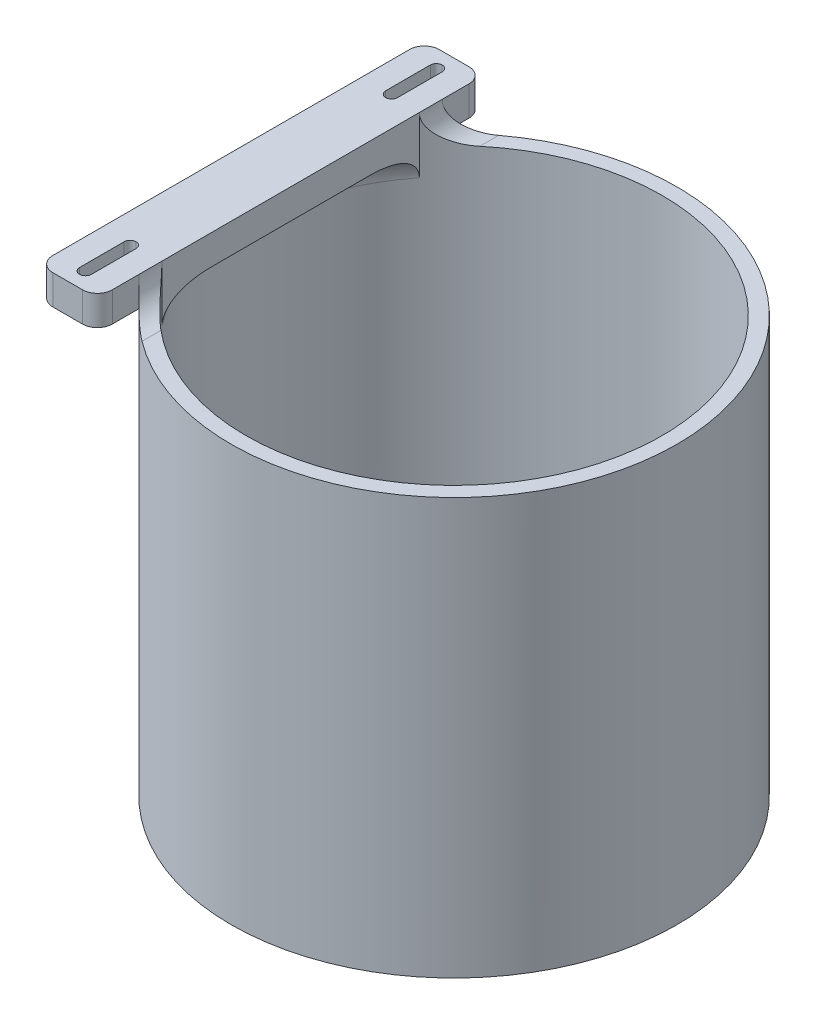
SolidWorks part; units mm, degrees
ref_plane "Front Plane" through (0, 0, 0) normal (0, 0, 1) x (1, 0, 0)
ref_plane "Top Plane" through (0, 0, 0) normal (0, 1, 0) x (1, 0, 0)
ref_plane "Right Plane" through (0, 0, 0) normal (1, 0, 0) x (0, 0, -1)
sketch "Sketch1" plane through (0, 0, 0) normal (0, 1, 0) x (1, 0, 0)
  circle A0 centre (0, 0) radius 70
  circle A1 centre (0, 0) radius 75
  dimension "D1" = 140
  dimension "D2" = 150
extrude "Boss-Extrude1" add sketch "Sketch1" along normal blind 140
sketch "Sketch2" plane through (0, 140, 0) normal (0, 1, 0) x (1, 0, 0)
  line L0 (0, 0) -> (-55, 0) construction
  line L2 (-55, -65) -> (-75, -65)
  line L3 (-55, -65) -> (-55, 65)
  line L4 (-55, 65) -> (-75, 65)
  line L5 (-75, -65) -> (-75, 65)
  line L6 (-55, -65) -> (-75, 65) construction
  line L7 (-55, 65) -> (-75, -65) construction
  point P4 (-65, 0)
  point P9 (-55, 0)
  dimension "D1" = 55
  dimension "D2" = 130
  dimension "D3" = 20
extrude "Boss-Extrude2" add sketch "Sketch2" along normal blind 10
fillet "Fillet1" radius 9 1 edges at (-70, 140, 0)
fillet "Fillet2" radius 10 2 edges at (-55, 140, 47.1457) (-55, 140, -47.1457)
fillet "Fillet3" radius 5 4 edges at (-75, 145, -65) (-55, 145, -65) (-55, 145, 65) (-75, 145, 65)
sketch "Sketch5" plane through (0, 150, 0) normal (0, 1, 0) x (1, 0, 0)
  line L2 (-65, -65) -> (-65, -61) construction
  line L3 (-67, -61) -> (-63, -61)
  line L4 (-67, -61) -> (-67, -42)
  line L5 (-67, -42) -> (-63, -42)
  line L6 (-63, -61) -> (-63, -42)
  line L7 (-67, -61) -> (-63, -42) construction
  line L8 (-67, -42) -> (-63, -61) construction
  line L9 (-70, -65) -> (-60, -65) construction
  point P0 (0, 0)
  point P1 (-65, -61)
  point P4 (-65, -51.5)
  dimension "D2" = 19
  dimension "D3" = 4
  dimension "D4" = 4
extrude "Cut-Extrude1" cut sketch "Sketch5" against normal blind 10
fillet "Fillet4" radius 2 4 edges at (-67, 145, 42) (-63, 145, 42) (-67, 145, 61) (-63, 145, 61)
mirror "Mirror4" about plane through (0, 0, 0) normal (0, 0, 1) of "Fillet4", "Cut-Extrude1"
